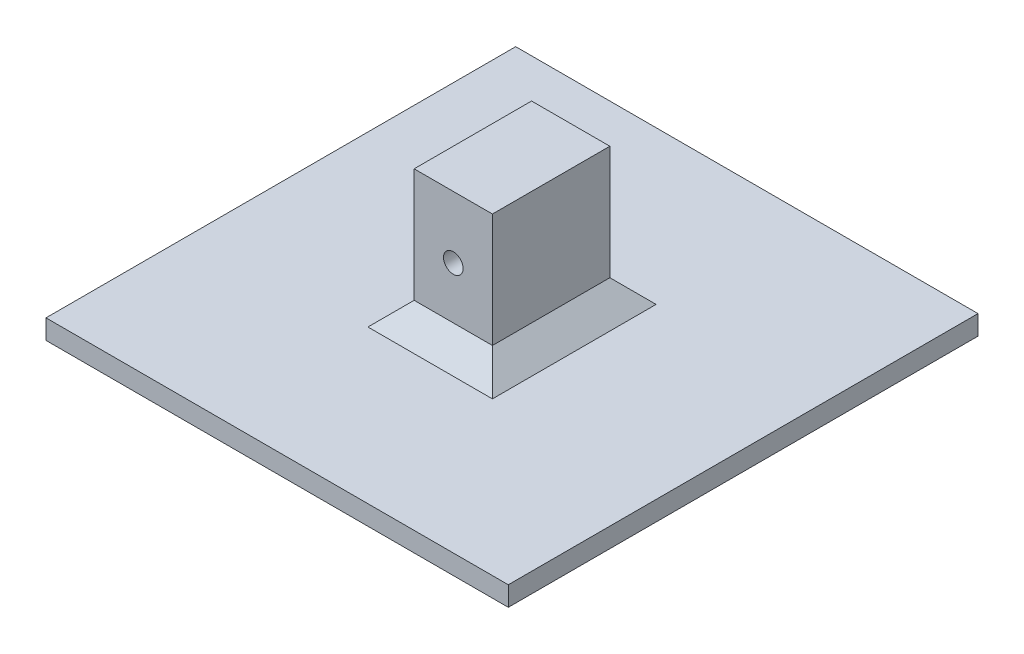
SolidWorks part; units mm, degrees
ref_plane "Front Plane" through (0, 0, 0) normal (0, 0, 1) x (1, 0, 0)
ref_plane "Top Plane" through (0, 0, 0) normal (0, 1, 0) x (1, 0, 0)
ref_plane "Right Plane" through (0, 0, 0) normal (1, 0, 0) x (0, 0, -1)
sketch "Sketch-Profile" plane through (0, 0, 0) normal (1, 0, 0) x (0, 0, -1)
  line L0 (-76.2, 6.35) -> (-76.2, 0)
  line L5 (-76.2, 6.35) -> (-19.05, 6.35)
  line L6 (-76.2, 0) -> (76.2, 0)
  line L7 (76.2, 6.35) -> (76.2, 0)
  line L8 (-76.2, 6.35) -> (76.2, 0) construction
  line L9 (-76.2, 0) -> (76.2, 6.35) construction
  line L10 (-19.05, 50.8) -> (-19.05, 6.35)
  line L11 (-19.05, 50.8) -> (19.05, 50.8)
  line L13 (19.05, 50.8) -> (19.05, 6.35)
  line L14 (-19.05, 50.8) -> (19.05, 6.35) construction
  line L15 (-19.05, 6.35) -> (19.05, 50.8) construction
  line L16 (19.05, 6.35) -> (76.2, 6.35)
  point P1 (0, 3.175)
  point P2 (0, 28.575)
  dimension "D1" = 6.35
  dimension "D2" = 50.8
  dimension "D3" = 152.4
  dimension "D4" = 38.1
extrude "Boss-Extrude1" add sketch "Sketch-Profile" along normal blind 12.7 and the other way blind 12.7
sketch "Sketch-Hole Location" plane through (0, 0, 19.05) normal (0, 0, 1) x (1, 0, 0)
  line L0 (0, 0) -> (0, 50.8) construction
  line L1 (12.7, 0) -> (-12.7, 0) construction
  line L2 (12.7, 50.8) -> (-12.7, 50.8) construction
  line L3 (118.2175, 30.6931) -> (31.7825, 30.6931) construction
  point P6 (0, 30.6931)
sketch "Sketch5" plane through (0, 0, 19.05) normal (0, 0, 1) x (1, 0, 0)
  point P0 (0, 30.6931)
hole_wizard "1/4 (0.25) Diameter Hole1" positions "Sketch5" profile "Sketch4" hole size "1/4" standard "ANSI Inch" end condition through all
sketch "Sketch4" plane through (0, 30.6931, 19.05) normal (1, 0, 0) x (0, -1, 0)
  line L0 (0, 0) -> (0, 95.25)
  line L1 (0, 95.25) -> (3.175, 95.25)
  line L2 (3.175, 95.25) -> (3.175, 0)
  line L5 (3.175, 0) -> (0, 0)
  line L11 (0, -6.35) -> (0, 107.95) construction
  dimension "Thru Hole Dia." = 6.35
  dimension "Thru Hole Depth" = 95.25
sketch "Sketch6" plane through (0, 0, 0) normal (1, 0, 0) x (0, 0, -1)
  line L0 (76.2, 0) -> (76.2, 6.35) construction
  line L1 (-76.2, 0) -> (76.2, 0) construction
  line L2 (-76.2, 6.35) -> (-76.2, 0) construction
  line L3 (76.2, 0) -> (76.2, 6.35)
  line L4 (-76.2, 0) -> (76.2, 0)
  line L5 (-76.2, 6.35) -> (-76.2, 0)
  line L6 (-76.2, 6.35) -> (76.2, 6.35)
extrude "Boss-Extrude2" add sketch "Sketch6" along normal blind 75 and the other way blind 75
chamfer "Chamfer1" distance 7.5 angle 45 4 edges at (0, 6.35, 19.05) (-12.7, 6.35, 0) (0, 6.35, -19.05) (12.7, 6.35, 0)
